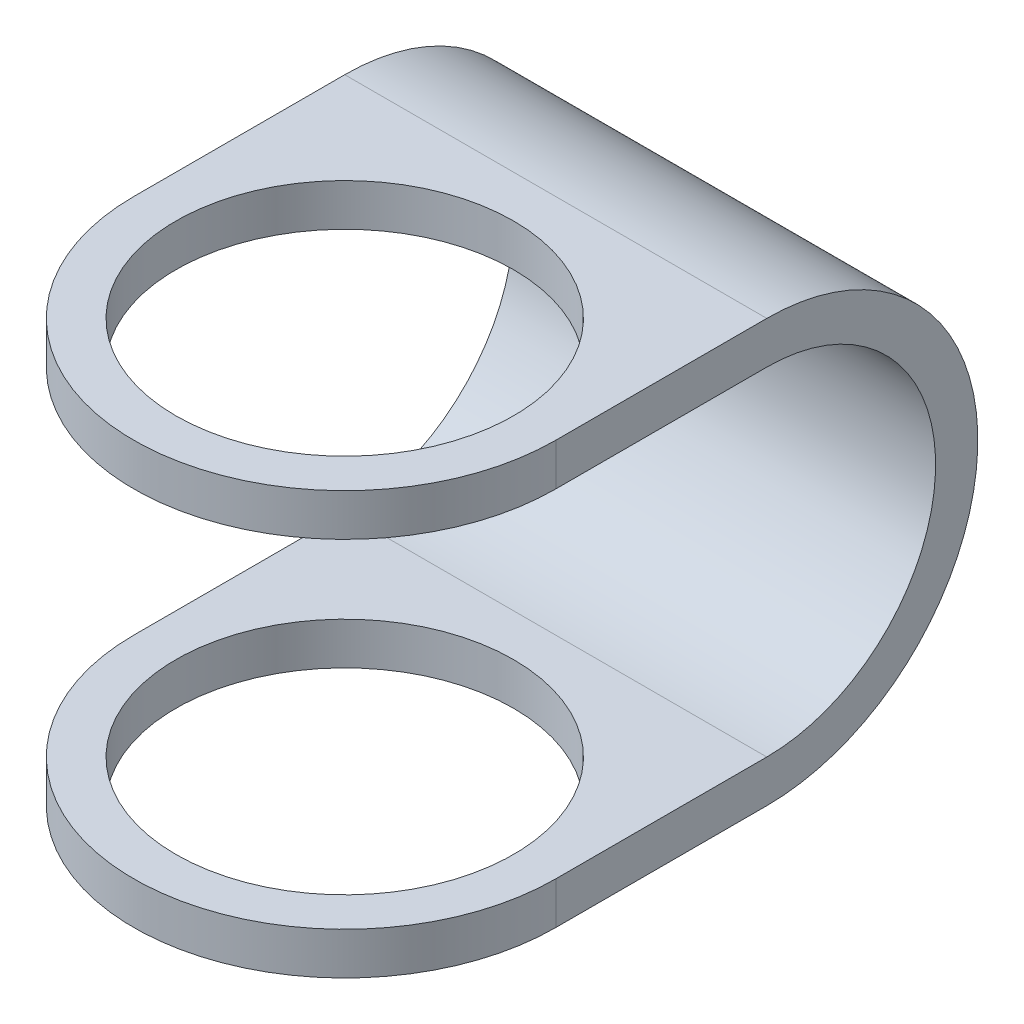
SolidWorks part; units mm, degrees
ref_plane "前基準面" through (0, 0, 0) normal (0, 0, 1) x (1, 0, 0)
ref_plane "上基準面" through (0, 0, 0) normal (0, 1, 0) x (1, 0, 0)
ref_plane "右基準面" through (0, 0, 0) normal (1, 0, 0) x (0, 0, -1)
sketch "草圖1" plane through (0, 0, 0) normal (1, 0, 0) x (0, 0, -1)
  line L0 (0, 50) -> (150, 50) construction
  line L1 (0, 0) -> (100, 0)
  line L2 (0, 0) -> (0, 100)
  line L3 (0, 100) -> (100, 100)
  arc A0 (100, 0) -> (100, 100) centre (100, 50) ccw
  dimension "D1" = 50
  dimension "D2" = 150
extrude "填料-伸長1" add sketch "草圖1" along normal blind 100
sketch "草圖2" plane through (100, 0, 0) normal (1, 0, 0) x (0, 0, -1)
  line L3 (-26.4383, 10) -> (-26.4383, 90)
  line L6 (10, 90) -> (10, 10)
  line L7 (10, 10) -> (100, 10)
  line L8 (100, 90) -> (10, 90)
  line L10 (-26.4383, 10) -> (100, 10)
  line L11 (100, 90) -> (-26.4383, 90)
  arc A2 (100, 10) -> (100, 90) centre (100, 50) ccw
  arc A3 (100, 10) -> (100, 90) centre (100, 50) ccw
  dimension "D1" = 10
extrude "除料-伸長1" cut sketch "草圖2" against normal through all
fillet "圓角1" 2 edges at (100, 95, 0) (0, 95, 0) type full round first side face at (100, 50, -61.25) second side face at (0, 50, -61.25) middle face at (50, 95, 0)
fillet "圓角2" 2 edges at (100, 5, 0) (0, 5, 0) type full round first side face at (100, 50, -73.75) second side face at (0, 50, -73.75) middle face at (50, 5, 0)
sketch "草圖3" plane through (0, 100, 0) normal (0, 1, 0) x (1, 0, 0)
  circle A0 centre (50, 50) radius 40
  dimension "D1" = 80
extrude "除料-伸長2" cut sketch "草圖3" against normal through all
